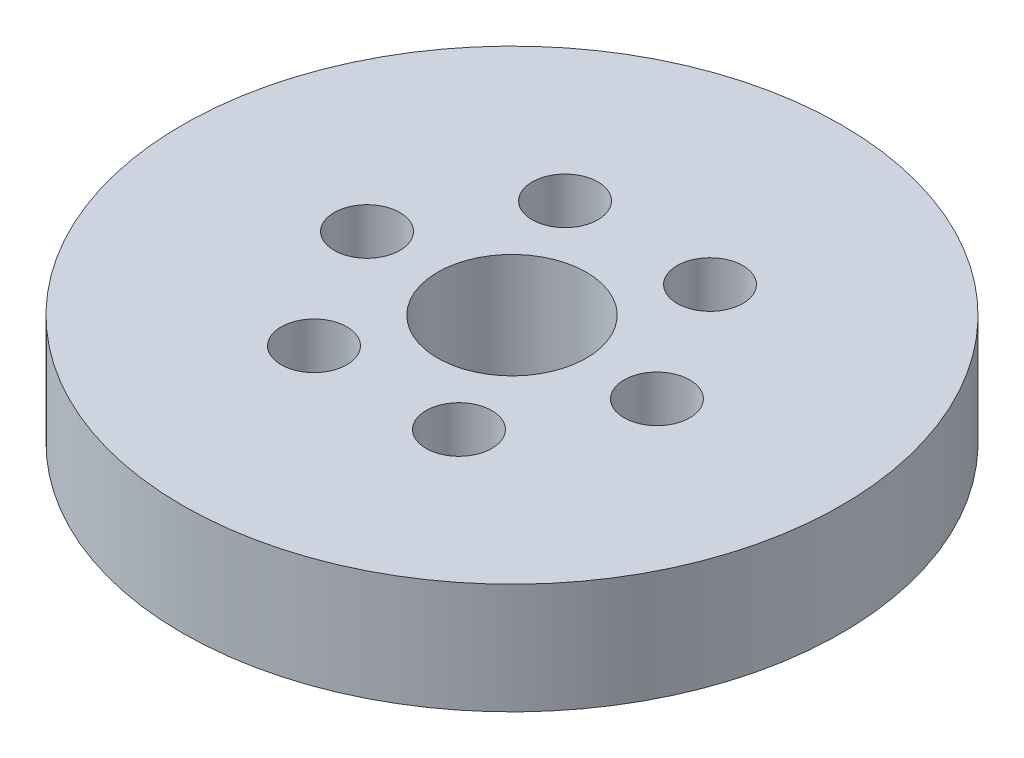
SolidWorks part; units mm, degrees
ref_plane "Front Plane" through (0, 0, 0) normal (0, 0, 1) x (1, 0, 0)
ref_plane "Top Plane" through (0, 0, 0) normal (0, 1, 0) x (1, 0, 0)
ref_plane "Right Plane" through (0, 0, 0) normal (1, 0, 0) x (0, 0, -1)
sketch "Sketch1" plane through (0, 0, 0) normal (0, 1, 0) x (1, 0, 0)
  circle A0 centre (0, 0) radius 77.5
  dimension "FLANGE_OD" = 155
extrude "Boss-Extrude1" add sketch "Sketch1" along normal blind 26
sketch "Sketch2" plane through (0, 0, 0) normal (0, 1, 0) x (1, 0, 0)
  circle A0 centre (0, 0) radius 17.5
  dimension "BORE_D" = 35
extrude "Cut-Extrude1" cut sketch "Sketch2" along normal through all
sketch "Sketch3" plane through (0, 26, 0) normal (0, 1, 0) x (1, 0, 0)
  circle A0 centre (0, 0) radius 34.0865 construction
  circle A1 centre (-34.0865, 0) radius 7.7295
  dimension "BOLT_D" = 15.4591
  dimension "BOLT_PCD" = 68.1731
extrude "Cut-Extrude2" cut sketch "Sketch3" against normal blind 21.908
pattern_circular "CirPattern1" count 6 over 360 about axis through (0, 0, 0) along (0, 1, 0) of "Cut-Extrude2"
